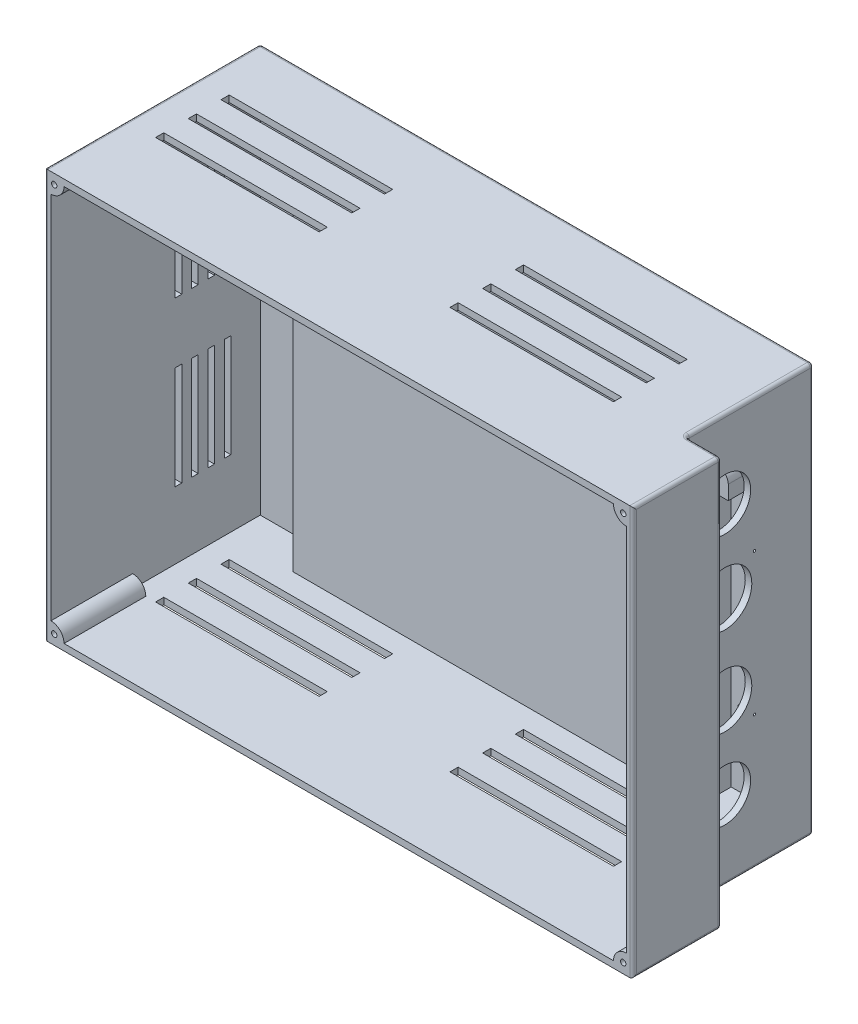
SolidWorks part; units mm, degrees
ref_plane "前视基准面" through (0, 0, 0) normal (0, 0, 1) x (1, 0, 0)
ref_plane "上视基准面" through (0, 0, 0) normal (0, 1, 0) x (1, 0, 0)
ref_plane "右视基准面" through (0, 0, 0) normal (1, 0, 0) x (0, 0, -1)
sketch "草图2" plane through (0, 0, 0) normal (0, 0, 1) x (1, 0, 0)
  line L1 (-90, 62.5) -> (90, 62.5)
  line L2 (-90, 62.5) -> (-90, -62.5)
  line L3 (-90, -62.5) -> (90, -62.5)
  line L4 (90, 62.5) -> (90, -62.5)
  line L5 (-90, 62.5) -> (90, -62.5) construction
  line L6 (-90, -62.5) -> (90, 62.5) construction
  point P0 (0, 0)
  dimension "D1" = 180
  dimension "D2" = 125
extrude "凸台-拉伸1" add sketch "草图2" along normal blind 66
sketch "草图3" plane through (0, 0, 0) normal (0, 0, -1) x (-1, 0, 0)
  line L0 (66, 59.5) -> (66, -59.5)
  line L1 (66, -59.5) -> (-54, -59.5)
  line L3 (66, 59.5) -> (-54, 59.5)
  line L4 (-54, -59.5) -> (-54, 59.5)
  line L5 (-90, 62.5) -> (90, 62.5) construction
  line L7 (90, -62.5) -> (-90, -62.5) construction
  line L9 (-90, -62.5) -> (-90, 62.5) construction
  line L11 (90, 62.5) -> (90, -62.5) construction
  dimension "D1" = 3
  dimension "D2" = 24
  dimension "D3" = 3
  dimension "D4" = 36
extrude "切除-拉伸1" cut sketch "草图3" against normal blind 10
sketch "草图4" plane through (90, 0, 0) normal (1, 0, 0) x (0, 0, -1)
  line L0 (-39, -62.5) -> (-39, 62.5)
  line L1 (-66, 61.5) -> (-66, -61.5) construction
  line L2 (-66, 62.5) -> (0, 62.5) construction
  line L4 (0, -62.5) -> (0, 62.5)
  line L6 (-66, 62.5) -> (-66, -62.5)
  line L9 (0, 62.5) -> (-39, 62.5)
  line L11 (-39, -62.5) -> (0, -62.5)
  line L14 (0, -62.5) -> (0, 62.5)
  line L15 (0, 62.5) -> (-66, 62.5)
  line L16 (-66, -62.5) -> (0, -62.5)
  dimension "D2" = 27
  dimension "D1" = 0
extrude "切除-拉伸2" cut sketch "草图4" against normal offset from surface (10.8 mm away) 2
shell "抽壳1" thickness 2 removed face at (0, 0, 66)
sketch "草图6" plane through (79.2, 0, 0) normal (1, 0, 0) x (0, 0, -1)
  line L1 (-16.0647, -23.6651) -> (-20.0647, -23.6651)
  line L2 (-16.0647, -23.6651) -> (-16.0647, -19.6651)
  line L3 (-16.0647, -19.6651) -> (-20.0647, -19.6651)
  line L4 (-20.0647, -23.6651) -> (-20.0647, -19.6651)
  line L5 (-34.2212, -23.6651) -> (-38.2212, -23.6651)
  line L6 (-34.2212, -23.6651) -> (-34.2212, -19.6651)
  line L7 (-34.2212, -19.6651) -> (-38.2212, -19.6651)
  line L8 (-38.2212, -23.6651) -> (-38.2212, -19.6651)
  line L9 (-34.2212, 19.6651) -> (-38.2212, 19.6651)
  line L10 (-34.2212, 19.6651) -> (-34.2212, 23.6651)
  line L11 (-34.2212, 23.6651) -> (-38.2212, 23.6651)
  line L12 (-38.2212, 19.6651) -> (-38.2212, 23.6651)
  line L13 (-16.0647, 19.6651) -> (-20.0647, 19.6651)
  line L14 (-16.0647, 19.6651) -> (-16.0647, 23.6651)
  line L15 (-16.0647, 23.6651) -> (-20.0647, 23.6651)
  line L16 (-20.0647, 19.6651) -> (-20.0647, 23.6651)
  arc A0 (-18.5647, 21.6651) -> (-17.5647, 21.6651) centre (-18.0647, 21.6651) ccw construction
  arc A1 (-17.5647, 21.6651) -> (-18.5647, 21.6651) centre (-18.0647, 21.6651) ccw construction
  arc A2 (-35.7212, 21.6651) -> (-36.7212, 21.6651) centre (-36.2212, 21.6651) ccw construction
  arc A3 (-36.7212, 21.6651) -> (-35.7212, 21.6651) centre (-36.2212, 21.6651) ccw construction
  arc A4 (-36.7212, -21.6651) -> (-35.7212, -21.6651) centre (-36.2212, -21.6651) ccw construction
  arc A5 (-18.5647, -21.6651) -> (-17.5647, -21.6651) centre (-18.0647, -21.6651) ccw construction
  dimension "D10" = 2
  dimension "D1" = 2
  dimension "D2" = 2
  dimension "D3" = 2
  dimension "D4" = 2
  dimension "D5" = 4
  dimension "D6" = 2
  dimension "D7" = 4
  dimension "D8" = 2
  dimension "D9" = 2
  dimension "D11" = 4
  dimension "D12" = 4
  dimension "D13" = 2
  dimension "D14" = 2
  dimension "D15" = 4
  dimension "D16" = 4
extrude "凸台-拉伸2" add sketch "草图6" against normal up to surface (3 mm away)
sketch "草图7" plane through (79.2, 0, 0) normal (1, 0, 0) x (0, 0, -1)
  circle A0 centre (-27.143, -13.5) radius 8.25
  circle A1 centre (-27.143, 13.5) radius 8.25
  circle A2 centre (-18.0647, -21.6651) radius 0.375
  circle A3 centre (-18.0647, 21.6651) radius 0.375
  circle A4 centre (-36.2212, 21.6651) radius 0.375
  circle A5 centre (-36.2212, -21.6651) radius 0.375
  arc A6 (-19.143, -13.5) -> (-35.143, -13.5) centre (-27.143, -13.5) ccw construction
  circle A7 centre (-27.143, 38.5) radius 7.9
  circle A8 centre (-27.143, 38.5) radius 7.65 construction
  circle A9 centre (-27.143, -38.5) radius 7.9
  dimension "D1" = 0.75
  dimension "D2" = 0.25
  dimension "D3" = 0.25
extrude "切除-拉伸3" cut sketch "草图7" against normal up to next
sketch "草图8" plane through (0, -62.5, 0) normal (0, -1, 0) x (1, 0, 0)
  line L0 (-90, 66) -> (90, 66) construction
  line L1 (-81, 41) -> (-31, 41)
  line L2 (-81, 41) -> (-81, 38.5)
  line L3 (-81, 38.5) -> (-31, 38.5)
  line L4 (-31, 41) -> (-31, 38.5)
  line L5 (-90, 66) -> (-90, 0) construction
  line L6 (9, 41) -> (59, 41)
  line L7 (9, 41) -> (9, 38.5)
  line L8 (9, 38.5) -> (59, 38.5)
  line L9 (59, 41) -> (59, 38.5)
  line L10 (9, 31) -> (59, 31)
  line L11 (9, 31) -> (9, 28.5)
  line L12 (9, 28.5) -> (59, 28.5)
  line L13 (59, 31) -> (59, 28.5)
  line L14 (9, 21) -> (59, 21)
  line L15 (9, 21) -> (9, 18.5)
  line L16 (9, 18.5) -> (59, 18.5)
  line L17 (59, 21) -> (59, 18.5)
  line L18 (-81, 31) -> (-31, 31)
  line L19 (-81, 31) -> (-81, 28.5)
  line L20 (-81, 28.5) -> (-31, 28.5)
  line L21 (-31, 31) -> (-31, 28.5)
  line L22 (-81, 21) -> (-31, 21)
  line L23 (-81, 21) -> (-81, 18.5)
  line L24 (-81, 18.5) -> (-31, 18.5)
  line L25 (-31, 21) -> (-31, 18.5)
  dimension "D1" = 2.5
  dimension "D2" = 25
  dimension "D3" = 9
  dimension "D4" = 50
  dimension "D5" = 2
  dimension "D6" = 3
extrude "切除-拉伸4" cut sketch "草图8" against normal up to surface (125 mm away) and the other way through all up to face at (26.4, 62.5, 35)
sketch "草图9" plane through (0, 0, 66) normal (0, 0, 1) x (1, 0, 0)
  line L1 (-88, 60.5) -> (-84, 60.5)
  line L2 (-88, 60.5) -> (-88, 56.5)
  line L5 (0, 0) -> (0, 36.715) construction
  line L6 (0, 0) -> (38.7304, 0) construction
  line L7 (-88, -60.5) -> (-88, -56.5)
  line L8 (-88, -60.5) -> (-84, -60.5)
  line L9 (88, -60.5) -> (84, -60.5)
  line L10 (88, -60.5) -> (88, -56.5)
  line L11 (88, 60.5) -> (88, 56.5)
  line L12 (88, 60.5) -> (84, 60.5)
  circle A0 centre (-87, 59.5) radius 0.825
  arc A1 (-84, 60.5) -> (-88, 56.5) centre (-88, 60.5) cw
  arc A2 (-84, -60.5) -> (-88, -56.5) centre (-88, -60.5) ccw
  circle A3 centre (-87, -59.5) radius 0.825
  circle A4 centre (87, -59.5) radius 0.825
  arc A5 (84, -60.5) -> (88, -56.5) centre (88, -60.5) cw
  arc A6 (84, 60.5) -> (88, 56.5) centre (88, 60.5) ccw
  circle A7 centre (87, 59.5) radius 0.825
  dimension "D1" = 1.65
  dimension "D2" = 1
  dimension "D3" = 1
  dimension "D4" = 4
extrude "凸台-拉伸3" add sketch "草图9" against normal up to surface (25 mm away) up to face at (82.6, 0, 41)
sketch "草图10" plane through (0, 0, 2) normal (0, 0, 1) x (1, 0, 0)
  line L0 (77.2, -60.5) -> (77.2, 60.5) construction
  line L1 (77.2, 50.5757) -> (70.499, 50.5757)
  line L2 (77.2, 50.5757) -> (77.2, 60.5)
  line L3 (77.2, 60.5) -> (70.499, 60.5)
  line L4 (70.499, 50.5757) -> (70.499, 60.5)
  line L5 (84, 60.5) -> (-84, 60.5) construction
  line L6 (56, 60.5) -> (56, -60.5) construction
  line L7 (62.513, 50.5757) -> (56, 50.5757)
  line L8 (62.513, 50.5757) -> (62.513, 60.5)
  line L9 (62.513, 60.5) -> (56, 60.5)
  line L10 (56, 50.5757) -> (56, 60.5)
  line L11 (62.513, 22.2546) -> (56, 22.2546)
  line L12 (62.513, 22.2546) -> (62.513, 29.6276)
  line L13 (62.513, 29.6276) -> (56, 29.6276)
  line L14 (56, 22.2546) -> (56, 29.6276)
  line L16 (77.2, 22.2546) -> (70.499, 22.2546)
  line L17 (77.2, 22.2546) -> (77.2, 29.6276)
  line L18 (77.2, 29.6276) -> (70.499, 29.6276)
  line L19 (70.499, 22.2546) -> (70.499, 29.6276)
  arc A0 (73.999, 27.2546) -> (73.999, 25.2546) centre (73.999, 26.2546) ccw construction
  arc A1 (59.013, 25.1276) -> (59.013, 27.1276) centre (59.013, 26.1276) ccw construction
  arc A2 (59.013, 27.1276) -> (59.013, 25.1276) centre (59.013, 26.1276) ccw construction
  arc A4 (74.126, 53.5757) -> (74.126, 55.5757) centre (74.126, 54.5757) ccw construction
  circle A5 centre (74.126, 54.5757) radius 0.825
  circle A6 centre (59.14, 54.5757) radius 0.825
  circle A7 centre (59.013, 26.1276) radius 0.825
  circle A8 centre (73.999, 26.2546) radius 0.825
  dimension "D7" = 1.65
  dimension "D6" = 1.65
  dimension "D8" = 1.65
  dimension "D9" = 1.65
  dimension "D1" = 4
  dimension "D2" = 3.5
  dimension "D3" = 3.5
  dimension "D4" = 3.5
  dimension "D5" = 4
extrude "开关螺孔凸台-拉伸4" add sketch "草图10" along normal up to surface (7.3999 mm away)
sketch "草图11" plane through (0, 0, 0) normal (0, 0, -1) x (-1, 0, 0)
  circle A0 centre (-66.76, 36.1607) radius 6.1
  circle A5 centre (-65.482, 49.2417) radius 2.6
  dimension "D1" = 12.2
  dimension "D2" = 5.2
extrude "切除-拉伸5" cut sketch "草图11" against normal up to next
fillet "圆角1" radius 3 4 edges at (62.513, 29.6276, 5.7) (62.513, 50.5757, 5.7) (70.499, 29.6276, 5.7) (70.499, 50.5757, 5.7)
fillet "圆角2" radius 1 26 edges at (90, 0, 66) (90, 0, 39) (79.2, 0, 39) (-90, 0, 66) (-90, -62.5, 33) (90, -62.5, 52.5) (84.6, -62.5, 39) (79.2, -62.5, 19.5) (-90, 62.5, 33) (79.2, 62.5, 19.5) (84.6, 62.5, 39) (90, 62.5, 52.5) (-5.4, 62.5, 0) (-90, 0, 0) (-5.4, -62.5, 0) (79.2, 0, 0) (-66, 0, 0) (-6, 59.5, 0) (54, 0, 0) (-6, -59.5, 0) (62.882, 49.2417, 0) (60.66, 36.1607, 0) (-6, 59.5, 10) (-66, 0, 10) (-6, -59.5, 10) (54, 0, 10)
sketch "草图12" plane through (-90, 0, 0) normal (-1, 0, 0) x (0, 0, 1)
  line L0 (1, 61.5) -> (1, -61.5) construction
  line L1 (11, 41.5) -> (13, 41.5)
  line L2 (11, 41.5) -> (11, 10)
  line L3 (11, 10) -> (13, 10)
  line L4 (13, 41.5) -> (13, 10)
  line L5 (65, 61.5) -> (1, 61.5) construction
  line L6 (16, 41.5) -> (18, 41.5)
  line L7 (16, 41.5) -> (16, 10)
  line L8 (16, 10) -> (18, 10)
  line L9 (18, 41.5) -> (18, 10)
  line L10 (21, 41.5) -> (23, 41.5)
  line L11 (21, 41.5) -> (21, 10)
  line L12 (21, 10) -> (23, 10)
  line L13 (23, 41.5) -> (23, 10)
  line L14 (26, 41.5) -> (28, 41.5)
  line L15 (26, 41.5) -> (26, 10)
  line L16 (26, 10) -> (28, 10)
  line L17 (28, 41.5) -> (28, 10)
  line L18 (16, -8.5) -> (18, -8.5)
  line L19 (16, -8.5) -> (16, -40)
  line L20 (16, -40) -> (18, -40)
  line L21 (18, -8.5) -> (18, -40)
  line L22 (21, -8.5) -> (23, -8.5)
  line L23 (21, -8.5) -> (21, -40)
  line L24 (21, -40) -> (23, -40)
  line L25 (23, -8.5) -> (23, -40)
  line L26 (26, -8.5) -> (28, -8.5)
  line L27 (26, -8.5) -> (26, -40)
  line L28 (26, -40) -> (28, -40)
  line L29 (28, -8.5) -> (28, -40)
  line L30 (11, -8.5) -> (13, -8.5)
  line L31 (11, -8.5) -> (11, -40)
  line L32 (11, -40) -> (13, -40)
  line L33 (13, -8.5) -> (13, -40)
  dimension "D1" = 2
  dimension "D2" = 31.5
  dimension "D3" = 10
  dimension "D4" = 20
  dimension "D5" = 4
  dimension "D6" = 2
extrude "切除-拉伸6" cut sketch "草图12" against normal up to next
